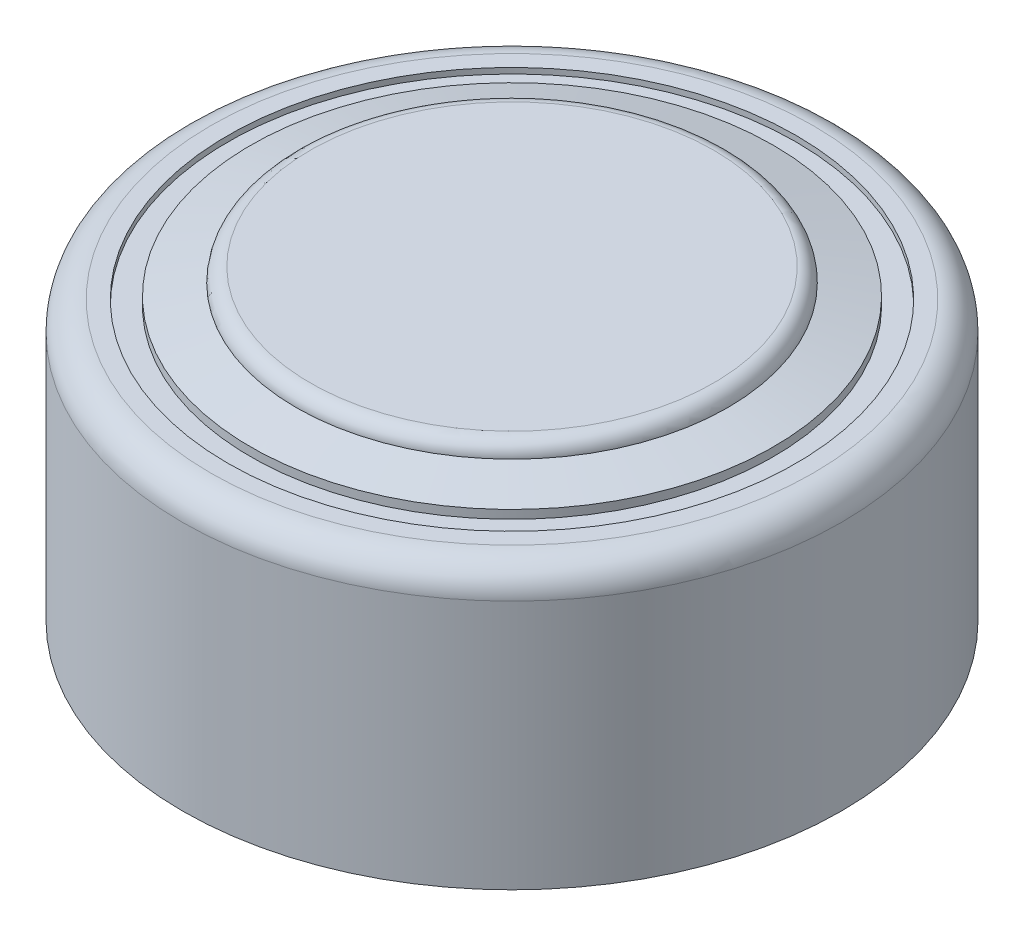
SolidWorks part; units mm, degrees
ref_plane "Front Plane" through (0, 0, 0) normal (0, 0, 1) x (1, 0, 0)
ref_plane "Top Plane" through (0, 0, 0) normal (0, 1, 0) x (1, 0, 0)
ref_plane "Right Plane" through (0, 0, 0) normal (1, 0, 0) x (0, 0, -1)
sketch "Croquis1" plane through (0, 0, 0) normal (0, 1, 0) x (1, 0, 0)
  circle A0 centre (0, 0) radius 5.8
  dimension "D1" = 11.6
extrude "Saliente-Extruir1" add sketch "Croquis1" along normal blind 4.9
fillet "Redondeo1" radius 0.5 1 edges at (0, 4.9, 5.8)
sketch "Croquis2" plane through (0, 4.9, 0) normal (0, 1, 0) x (1, 0, 0)
  circle A3 centre (0, 0) radius 5
  dimension "D2" = 10
extrude "Cortar-Extruir1" cut sketch "Croquis2" against normal blind 0.1
sketch "Croquis3" plane through (0, 0, 0) normal (0, -1, 0) x (1, 0, 0)
  circle A0 centre (0, 0) radius 4.6
  dimension "D1" = 9.2
extrude "Saliente-Extruir2" add sketch "Croquis3" against normal blind 5.15
sketch "Croquis4" plane through (0, 0, 0) normal (0, -1, 0) x (1, 0, 0)
  circle A0 centre (0, 0) radius 3.8
  dimension "D1" = 7.6
extrude "Saliente-Extruir3" add sketch "Croquis4" against normal blind 5.4
fillet "Redondeo7" radius 0.25 1 edges at (0, 5.4, -3.8)
chamfer "Chaflán1" distance 0.8 distance2 0.2 1 edges at (0, 5.15, -4.6) first distance on face at (0, 5.15, -3.8)
